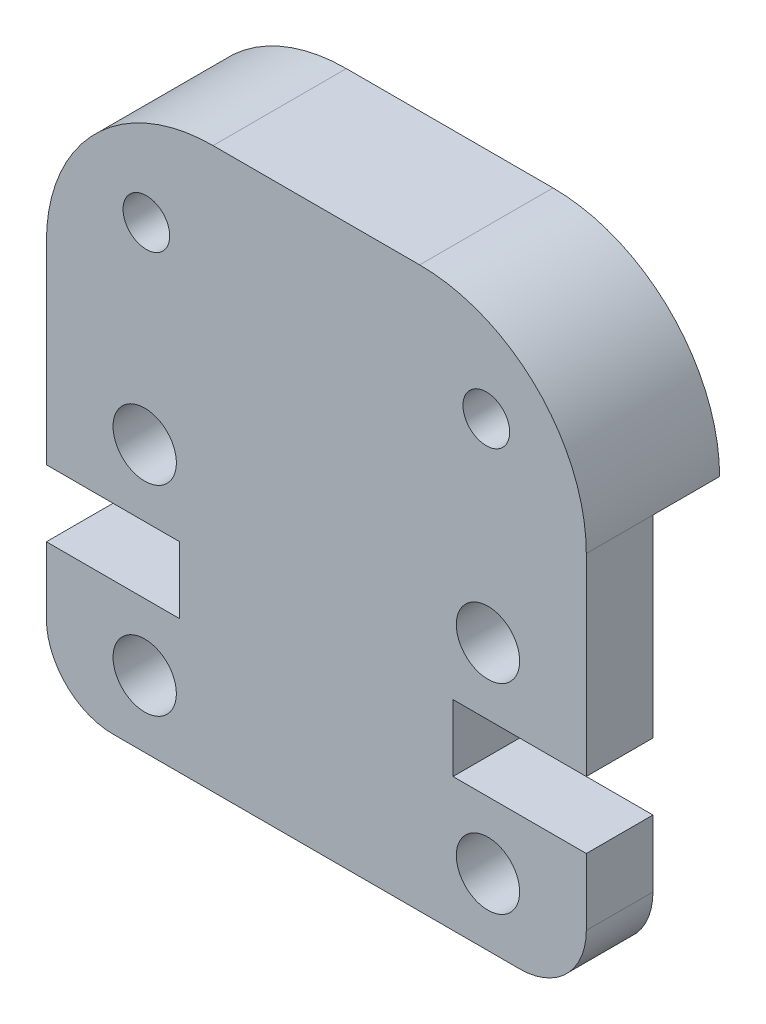
SolidWorks part; units mm, degrees
ref_plane "Front Plane" through (0, 0, 0) normal (0, 0, 1) x (1, 0, 0)
ref_plane "Top Plane" through (0, 0, 0) normal (0, 1, 0) x (1, 0, 0)
ref_plane "Right Plane" through (0, 0, 0) normal (1, 0, 0) x (0, 0, -1)
sketch "Sketch1" plane through (0, 0, 0) normal (0, 0, 1) x (1, 0, 0)
  line L0 (0, 6) -> (0, 11.795)
  line L1 (12.2, 4) -> (16.2, 4)
  line L2 (5, 16.795) -> (11.2, 16.795)
  line L3 (2, 0) -> (14.2, 0)
  line L4 (12.2, 6) -> (12.2, 4)
  line L5 (0, 2) -> (0, 4)
  line L6 (0, 6) -> (4, 6)
  line L7 (16.2, 6) -> (12.2, 6)
  line L8 (4, 6) -> (4, 4)
  line L9 (4, 4) -> (0, 4)
  line L10 (16.2, 2) -> (16.2, 4)
  line L11 (16.2, 6) -> (16.2, 11.795)
  line L12 (8.1, 16.795) -> (8.1, 0) construction
  circle A0 centre (13.25, 2) radius 0.95
  arc A1 (5, 16.795) -> (0, 11.795) centre (5, 11.795) ccw
  circle A2 centre (13.25, 8) radius 0.95
  circle A3 centre (3, 13.795) radius 0.7
  arc A4 (16.2, 2) -> (14.2, 0) centre (14.2, 2) cw
  arc A5 (0, 2) -> (2, 0) centre (2, 2) ccw
  circle A6 centre (13.2, 13.795) radius 0.7
  circle A7 centre (2.95, 8) radius 0.95
  arc A8 (11.2, 16.795) -> (16.2, 11.795) centre (11.2, 11.795) cw
  circle A9 centre (2.95, 2) radius 0.95
  dimension "D1" = 1.9
  dimension "D2" = 1.4
  dimension "D3" = 5
  dimension "D4" = 2
  dimension "D5" = 3
  dimension "D6" = 8.1
  dimension "D7" = 8
  dimension "D9" = 16.795
  dimension "D8" = 3
extrude "Boss-Extrude1" add sketch "Sketch1" along normal blind 4
sketch "Sketch2" plane through (0, 0, 0) normal (0, 0, 1) x (1, 0, 0)
  line L0 (0, 0) -> (0, 11.795)
  line L1 (0, 11.795) -> (16.2, 11.795)
  line L2 (16.2, 11.795) -> (16.2, 0)
  line L3 (16.2, 0) -> (0, 0)
extrude "Cut-Extrude1" cut sketch "Sketch2" along normal blind 2
equation "\"D6@Sketch1\"= \"fingerWidth@parametersSketch@prostheticParameters.SLDPRT\" / 2 'DIP width"
equation "\"D9@Sketch1\"= \"HL@parametersSketch@prostheticParameters.SLDPRT\" * 0.107 - 3 'DIP length - Sil. Sht DIP"
equation "\"D1@Sketch1\"= 1.5 + \"tol1@parametersSketch@prostheticParameters.SLDPRT\""
equation "\"D2@Sketch1\"= 1 + \"tol1@parametersSketch@prostheticParameters.SLDPRT\""
